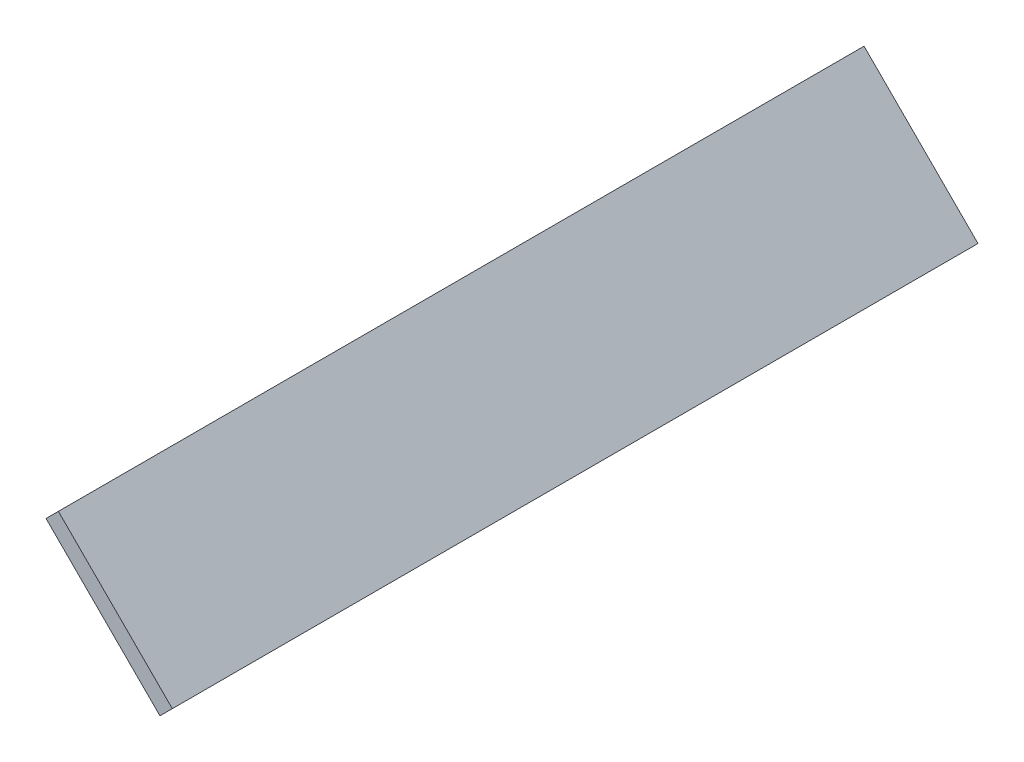
SolidWorks part; units mm, degrees
ref_plane "Front Plane" through (0, 0, 0) normal (0, 0, 1) x (1, 0, 0)
ref_plane "Top Plane" through (0, 0, 0) normal (0, 1, 0) x (1, 0, 0)
ref_plane "Right Plane" through (0, 0, 0) normal (1, 0, 0) x (0, 0, -1)
sketch "Sketch1" plane through (0, 0, 0) normal (0, 0, 1) x (1, 0, 0)
  line L0 (66.9029, 45.85) -> (108.2121, 4.5408)
  line L1 (66.9029, 45.85) -> (71.393, 50.3401)
  line L2 (108.2121, 4.5408) -> (112.7022, 9.0309)
  line L3 (71.393, 50.3401) -> (112.7022, 9.0309)
  line L4 (76.7812, -26.8901) -> (72.2911, -22.4) construction
extrude "Boss-Extrude1" add sketch "Sketch1" along normal up to surface (292.1 mm away)
